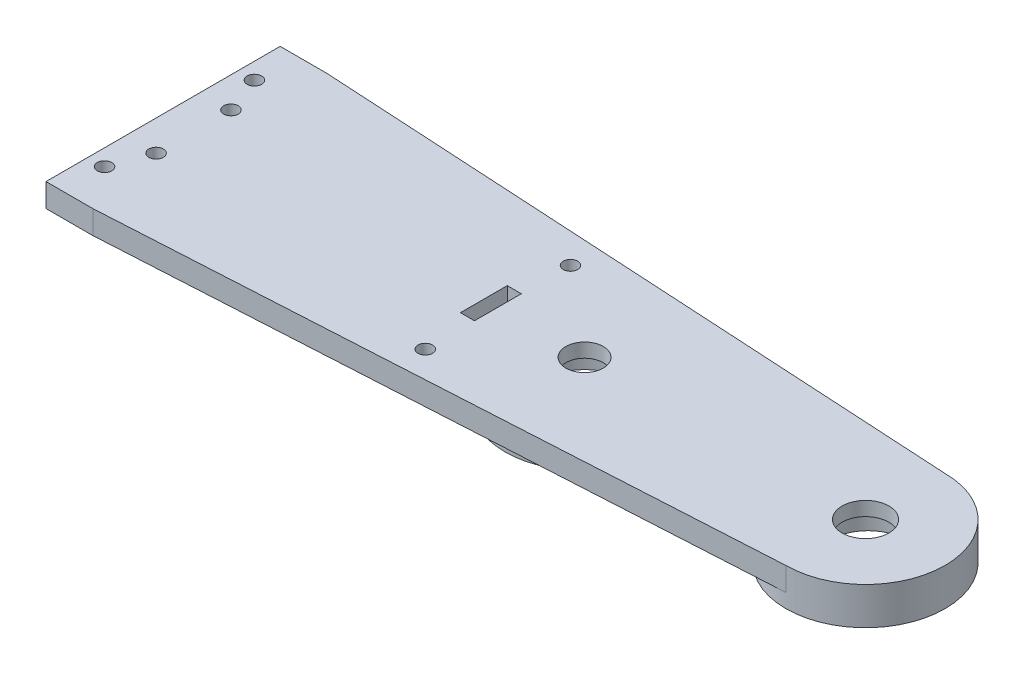
SolidWorks part; units mm, degrees
ref_plane "Front Plane" through (0, 0, 0) normal (0, 0, 1) x (1, 0, 0)
ref_plane "Top Plane" through (0, 0, 0) normal (0, 1, 0) x (1, 0, 0)
ref_plane "Right Plane" through (0, 0, 0) normal (1, 0, 0) x (0, 0, -1)
sketch "Sketch28" plane through (-32, 0, 0) normal (0, -1, 0) x (0, 0, 1)
  line L1 (0, -75) -> (0, -135) construction
  line L2 (-8, 8.5) -> (8, 8.5) construction
  line L3 (0, -75) -> (0, 15) construction
  line L8 (-25, 15) -> (25, 15)
  line L12 (25, 15) -> (25, 5)
  line L13 (-25, 15) -> (-25, 5)
  line L14 (-25, 5) -> (-17, -135)
  line L15 (17, -135) -> (25, 5)
  line L16 (-25, 5) -> (-25, 8.5) construction
  line L17 (-25, 8.5) -> (-8, 8.5) construction
  line L18 (-25, 15) -> (-25, 11.5) construction
  line L19 (-25, 11.5) -> (-16, 11.5) construction
  line L20 (-16, 11.5) -> (16, 11.5) construction
  line L21 (0, -75) -> (0, -56.5) construction
  line L22 (5, -56.5) -> (-5, -56.5)
  line L23 (-5, -56.5) -> (-5, -53.5)
  line L24 (-5, -53.5) -> (5, -53.5)
  line L25 (5, -53.5) -> (5, -56.5)
  line L26 (-5, -53.5) -> (-15.5, -53.5) construction
  line L27 (-15.5, -53.5) -> (-15.5, -56.5) construction
  line L28 (5, -53.5) -> (15.5, -53.5) construction
  line L29 (15.5, -53.5) -> (15.5, -56.5) construction
  circle A0 centre (0, -135) radius 5
  circle A3 centre (0, -75) radius 4
  arc A6 (17, -135) -> (-17, -135) centre (0, -135) cw
  circle A7 centre (8, 8.5) radius 1.55
  circle A8 centre (-8, 8.5) radius 1.55
  circle A9 centre (16, 11.5) radius 1.55
  circle A10 centre (-16, 11.5) radius 1.55
  circle A11 centre (-15.5, -56.5) radius 1.55
  circle A12 centre (15.5, -56.5) radius 1.55
  point P7 (0, 15)
  point P13 (0, 15)
  point P29 (0, -56.5)
extrude "Boss-Extrude10" add sketch "Sketch28" along normal blind 5
sketch "Sketch25" plane through (0, -5, 0) normal (0, -1, 0) x (0, 0, 1)
  circle A7 centre (0, -103) radius 17
extrude "Boss-Extrude8" add sketch "Sketch25" along normal blind 3
sketch "Sketch30" plane through (0, -5, 0) normal (0, -1, 0) x (0, 0, 1)
  circle A1 centre (0, -43) radius 17
extrude "Boss-Extrude11" add sketch "Sketch30" along normal blind 4
sketch "Sketch32" plane through (0, -9, 0) normal (0, -1, 0) x (1, 0, 0)
  circle A0 centre (43, 0) radius 9.5
extrude "Cut-Extrude3" cut sketch "Sketch32" against normal blind 6
sketch "Sketch33" plane through (0, -8, 0) normal (0, -1, 0) x (1, 0, 0)
  circle A0 centre (103, -0.5493) radius 8
extrude "Cut-Extrude4" cut sketch "Sketch33" against normal blind 5
